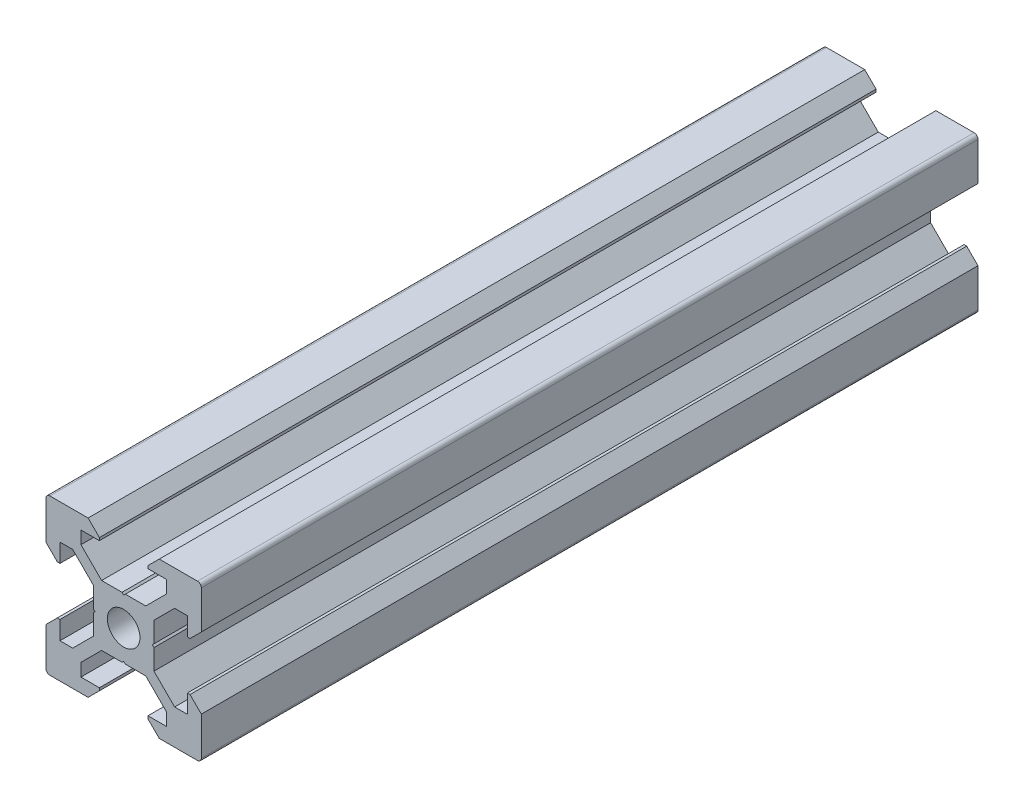
SolidWorks part; units mm, degrees
material "6061-T6 (SS)"
ref_plane "Front Plane" through (0, 0, 0) normal (0, 0, 1) x (1, 0, 0)
ref_plane "Top Plane" through (0, 0, 0) normal (0, 1, 0) x (1, 0, 0)
ref_plane "Right Plane" through (0, 0, 0) normal (1, 0, 0) x (0, 0, -1)
sketch "Sketch1" plane through (0, 0, 0) normal (0, 0, 1) x (1, 0, 0)
  line L1 (9.5, -10) -> (-9.5, -10)
  line L2 (10, -9.5) -> (10, 9.5)
  line L3 (9.5, 10) -> (-9.5, 10)
  line L4 (-10, -9.5) -> (-10, 9.5)
  line L5 (10, -10) -> (-10, 10) construction
  line L6 (10, 10) -> (-10, -10) construction
  circle A0 centre (0, 0) radius 2.1
  arc A1 (-9.5, 10) -> (-10, 9.5) centre (-9.5, 9.5) ccw
  arc A2 (10, 9.5) -> (9.5, 10) centre (9.5, 9.5) ccw
  arc A3 (9.5, -10) -> (10, -9.5) centre (9.5, -9.5) ccw
  arc A4 (-9.5, -10) -> (-10, -9.5) centre (-9.5, -9.5) cw
  point P0 (0, 0)
  line B0 (0, 0) -> (0, 10) construction
  line B1 (0, 3.69) -> (-0.21, 3.9)
  line B2 (-0.21, 3.9) -> (-2.8393, 3.9)
  line B3 (-2.8393, 3.9) -> (-5.5, 6.5607)
  line B4 (-5.5, 6.5607) -> (-5.5, 8.2)
  line B5 (-5.5, 8.2) -> (-3.125, 8.2)
  line B6 (-3.125, 8.2) -> (-3.125, 8.545)
  line B7 (-3.125, 8.545) -> (-4.58, 10)
  line B8 (-4.58, 10) -> (4.58, 10)
  line B9 (0, 0) -> (-5.9132, 5.9132) construction
  line B10 (3.125, 8.545) -> (4.58, 10)
  line B11 (3.125, 8.2) -> (3.125, 8.545)
  line B12 (5.5, 8.2) -> (3.125, 8.2)
  line B13 (5.5, 6.5607) -> (5.5, 8.2)
  line B14 (2.8393, 3.9) -> (5.5, 6.5607)
  line B15 (0.21, 3.9) -> (2.8393, 3.9)
  line B16 (0, 3.69) -> (0.21, 3.9)
  line B17 (0, 0) -> (-10, 0) construction
  line B18 (-3.69, 0) -> (-3.9, -0.21)
  line B19 (-3.9, -0.21) -> (-3.9, -2.8393)
  line B20 (-3.9, -2.8393) -> (-6.5607, -5.5)
  line B21 (-6.5607, -5.5) -> (-8.2, -5.5)
  line B22 (-8.2, -5.5) -> (-8.2, -3.125)
  line B23 (-8.2, -3.125) -> (-8.545, -3.125)
  line B24 (-8.545, -3.125) -> (-10, -4.58)
  line B25 (-10, -4.58) -> (-10, 4.58)
  line B26 (0, 0) -> (-5.9132, -5.9132) construction
  line B27 (-8.545, 3.125) -> (-10, 4.58)
  line B28 (-8.2, 3.125) -> (-8.545, 3.125)
  line B29 (-8.2, 5.5) -> (-8.2, 3.125)
  line B30 (-6.5607, 5.5) -> (-8.2, 5.5)
  line B31 (-3.9, 2.8393) -> (-6.5607, 5.5)
  line B32 (-3.9, 0.21) -> (-3.9, 2.8393)
  line B33 (-3.69, 0) -> (-3.9, 0.21)
  line B34 (0, 0) -> (0, -10) construction
  line B35 (0, -3.69) -> (0.21, -3.9)
  line B36 (0.21, -3.9) -> (2.8393, -3.9)
  line B37 (2.8393, -3.9) -> (5.5, -6.5607)
  line B38 (5.5, -6.5607) -> (5.5, -8.2)
  line B39 (5.5, -8.2) -> (3.125, -8.2)
  line B40 (3.125, -8.2) -> (3.125, -8.545)
  line B41 (3.125, -8.545) -> (4.58, -10)
  line B42 (4.58, -10) -> (-4.58, -10)
  line B43 (0, 0) -> (5.9132, -5.9132) construction
  line B44 (-3.125, -8.545) -> (-4.58, -10)
  line B45 (-3.125, -8.2) -> (-3.125, -8.545)
  line B46 (-5.5, -8.2) -> (-3.125, -8.2)
  line B47 (-5.5, -6.5607) -> (-5.5, -8.2)
  line B48 (-2.8393, -3.9) -> (-5.5, -6.5607)
  line B49 (-0.21, -3.9) -> (-2.8393, -3.9)
  line B50 (0, -3.69) -> (-0.21, -3.9)
  line B51 (0, 0) -> (10, 0) construction
  line B52 (3.69, 0) -> (3.9, 0.21)
  line B53 (3.9, 0.21) -> (3.9, 2.8393)
  line B54 (3.9, 2.8393) -> (6.5607, 5.5)
  line B55 (6.5607, 5.5) -> (8.2, 5.5)
  line B56 (8.2, 5.5) -> (8.2, 3.125)
  line B57 (8.2, 3.125) -> (8.545, 3.125)
  line B58 (8.545, 3.125) -> (10, 4.58)
  line B59 (10, 4.58) -> (10, -4.58)
  line B60 (0, 0) -> (5.9132, 5.9132) construction
  line B61 (8.545, -3.125) -> (10, -4.58)
  line B62 (8.2, -3.125) -> (8.545, -3.125)
  line B63 (8.2, -5.5) -> (8.2, -3.125)
  line B64 (6.5607, -5.5) -> (8.2, -5.5)
  line B65 (3.9, -2.8393) -> (6.5607, -5.5)
  line B66 (3.9, -0.21) -> (3.9, -2.8393)
  line B67 (3.69, 0) -> (3.9, -0.21)
  dimension "D1" = 4.2
  dimension "D3" = 0.5
  dimension "D2" = 20
sketch_block_instance "V Slot 1-4"
sketch_block "V Slot 1" parameters "D1"=10, "D2"=11, "D3"=4.3, "D4"=1.8, "D5"=0.21, "D6"=45, "D7"=9.16, "D8"=1.5, "D9"=6.25
sketch_block_instance "V Slot 1-5"
sketch_block_instance "V Slot 1-6"
sketch_block_instance "V Slot 1-7"
extrude "Boss-Extrude1" add sketch "Sketch1" along normal mid plane 100 contours B67 B52 B53 B54 B55 B56 B57 B58 L2 A2 L3 B10 B11 B12 B13 B14 B15 B16 B1 B2 B3 B4 B5 B6 B7 A1 L4 B27 B28 B29 B30 B31 B32 B33 B18 B19 B20 B21 B22 B23 B24 A4 L1 B44 B45 B46 B47 B48 B49 region at (7.04, -9.7172, 0)
